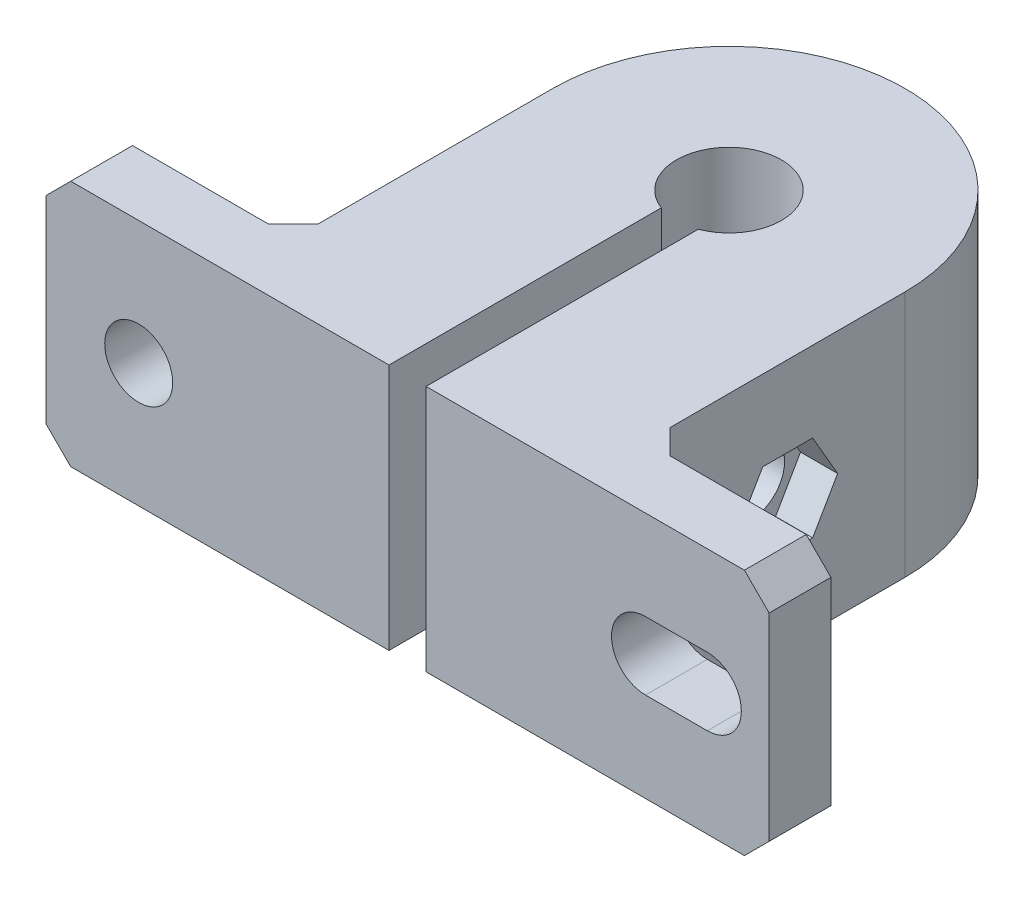
SolidWorks part; units mm, degrees
ref_plane "Front Plane" through (0, 0, 0) normal (0, 0, 1) x (1, 0, 0)
ref_plane "Top Plane" through (0, 0, 0) normal (0, 1, 0) x (1, 0, 0)
ref_plane "Right Plane" through (0, 0, 0) normal (1, 0, 0) x (0, 0, -1)
sketch "Sketch1" plane through (0, 0, 0) normal (0, 1, 0) x (1, 0, 0)
  line L0 (-14.25, 0) -> (-14.25, -26)
  line L1 (-14.25, -26) -> (14.25, -26)
  line L2 (14.25, -26) -> (14.25, 0)
  circle A0 centre (0, 0) radius 4.25
  arc A1 (14.25, 0) -> (-14.25, 0) centre (0, 0) ccw
  dimension "D1" = 8.5
  dimension "D2" = 10
  dimension "D3" = 26
extrude "Boss-Extrude1" add sketch "Sketch1" along normal blind 20
sketch "Sketch3" plane through (0, 20, 0) normal (0, 1, 0) x (1, 0, 0)
  line L0 (0, -26) -> (0, 0)
  line L1 (-14.25, -26) -> (14.25, -26) construction
extrude "Cut-Extrude-Thin1" cut sketch "Sketch3" against normal blind 20 and the other way through all thin thin type mid plane wall 3
sketch "Sketch4" plane through (0, 0, 26) normal (0, 0, 1) x (1, 0, 0)
  line L0 (-14.25, 20) -> (-14.25, 0) construction
  line L1 (-1.5, 0) -> (-29.25, 0)
  line L2 (-1.5, 0) -> (-1.5, 20)
  line L3 (-1.5, 20) -> (-29.25, 20)
  line L4 (-29.25, 0) -> (-29.25, 20)
  dimension "D1" = 15
extrude "Boss-Extrude2" add sketch "Sketch4" against normal blind 5
mirror "Mirror1" about plane through (0, 0, 0) normal (1, 0, 0) of "Boss-Extrude2"
sketch "Sketch5" plane through (0, 0, 21) normal (0, 0, -1) x (-1, 0, 0)
  line L0 (14.25, 20) -> (29.25, 0) construction
  line L1 (-29.25, 20) -> (-14.25, 0) construction
  line L2 (-24.25, 10) -> (-19.25, 10) construction
  line L3 (-24.25, 12.75) -> (-19.25, 12.75)
  line L4 (-24.25, 7.25) -> (-19.25, 7.25)
  circle A0 centre (21.75, 10) radius 2.75
  arc A1 (-24.25, 12.75) -> (-24.25, 7.25) centre (-24.25, 10) ccw
  arc A2 (-19.25, 7.25) -> (-19.25, 12.75) centre (-19.25, 10) ccw
  point P12 (-21.75, 10)
  dimension "D1" = 5.5
  dimension "D2" = 2.75
  dimension "D3" = 5
extrude "Cut-Extrude1" cut sketch "Sketch5" against normal blind 5
chamfer "Chamfer1" distance 2 angle 45 2 edges at (-14.25, 10, 21) (14.25, 10, 21)
chamfer "Chamfer2" distance 2 angle 45 4 edges at (29.25, 0, 23.5) (29.25, 20, 23.5) (-29.25, 0, 23.5) (-29.25, 20, 23.5)
sketch "Sketch6" plane through (14.25, 0, 0) normal (1, 0, 0) x (0, 0, -1)
  line L0 (-19, 20) -> (0, 0) construction
  circle A0 centre (-9.5, 10) radius 2.75
  dimension "D1" = 5.5
extrude "Cut-Extrude2" cut sketch "Sketch6" against normal blind 35
sketch "Sketch7" plane through (14.25, 0, 0) normal (1, 0, 0) x (0, 0, -1)
  line L1 (-13.5415, 10) -> (-11.5207, 6.5)
  line L2 (-11.5207, 6.5) -> (-7.4793, 6.5)
  line L3 (-7.4793, 6.5) -> (-5.4585, 10)
  line L4 (-5.4585, 10) -> (-7.4793, 13.5)
  line L5 (-7.4793, 13.5) -> (-11.5207, 13.5)
  line L6 (-11.5207, 13.5) -> (-13.5415, 10)
  circle A0 centre (-9.5, 10) radius 3.5 construction
  dimension "D1" = 7
extrude "Cut-Extrude3" cut sketch "Sketch7" against normal blind 3
sketch "Sketch8" plane through (-14.25, 0, 0) normal (-1, 0, 0) x (0, 0, 1)
  circle A0 centre (9.5, 10) radius 4
  dimension "D1" = 8
extrude "Cut-Extrude4" cut sketch "Sketch8" against normal blind 4
